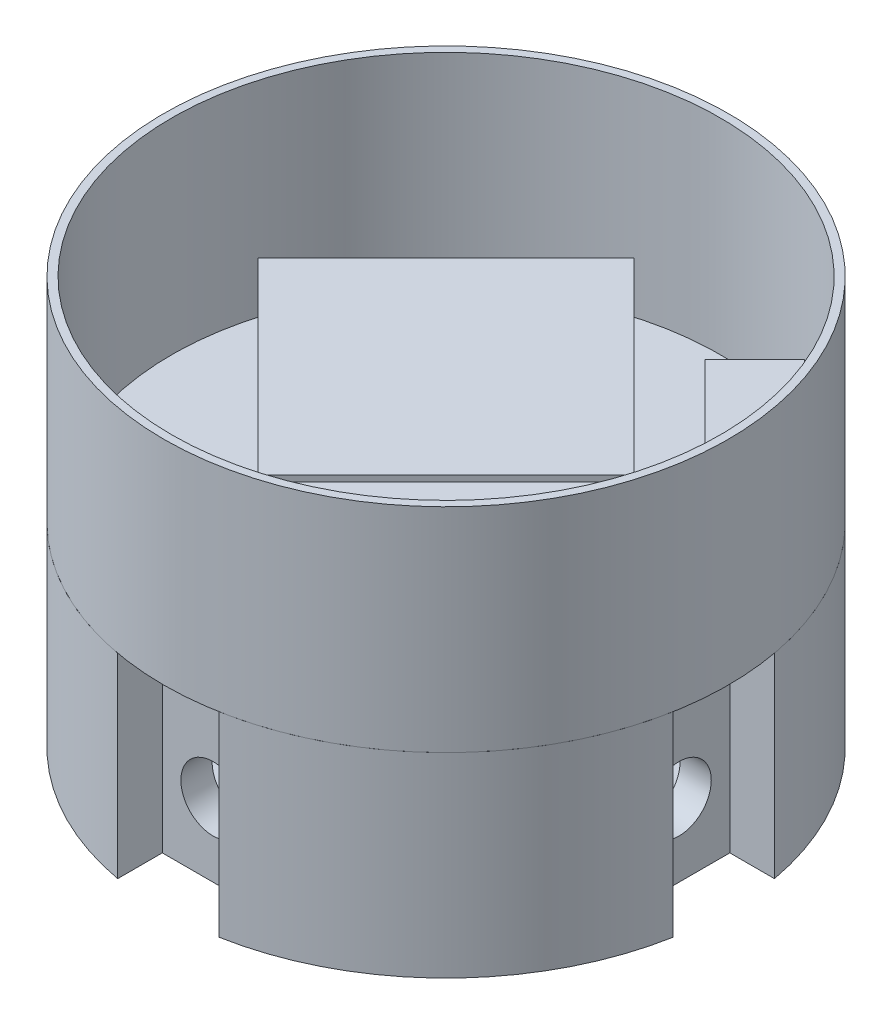
SolidWorks part; units mm, degrees
ref_plane "前基準面" through (0, 0, 0) normal (0, 0, 1) x (1, 0, 0)
ref_plane "上基準面" through (0, 0, 0) normal (0, 1, 0) x (1, 0, 0)
ref_plane "右基準面" through (0, 0, 0) normal (1, 0, 0) x (0, 0, -1)
sketch "草圖1" plane through (0, 0, 0) normal (0, 1, 0) x (1, 0, 0)
  line L0 (0, 78.355) -> (0, -92.3476) construction
  line L1 (-97.6496, 0) -> (95.3358, 0) construction
  line L21 (0, 48.0833) -> (-48.0833, 0)
  line L22 (-48.0833, 0) -> (0, -48.0833)
  line L23 (0, -48.0833) -> (48.0833, 0)
  line L24 (48.0833, 0) -> (0, 48.0833)
  line L26 (0, 0) -> (24.0416, 24.0416) construction
  circle A0 centre (0, 0) radius 72.25
  circle A1 centre (0, 0) radius 71
  circle A2 centre (0, 0) radius 68
  circle A4 centre (0, 0) radius 73 construction
  point P7 (0, 0)
  point P17 (0, 42.4264)
  point P19 (0, 0)
  point P23 (-73, 0)
  point P24 (-72.25, 0)
  point P25 (-71, 0)
  point P26 (34, 0)
  point P27 (-34, 0)
  point P28 (-68, 0)
  point P31 (42.4264, 0)
  point P32 (0, -42.4264)
  point P33 (-42.4264, 0)
  point P34 (0, 0)
  dimension "D1" = 144.5
  dimension "D5" = 142
  dimension "D6" = 3
  dimension "D8" = 146
  dimension "D2" = 68
  dimension "D3" = 4
  dimension "D4" = 4
sketch "草圖4" plane through (0, 0, 0) normal (0, 0, 1) x (1, 0, 0)
  line L0 (-34, 0) -> (-34, 102.5)
  line L1 (73, 0) -> (-73, 0) construction
  line L3 (34, 0) -> (34, 102.5)
  line L4 (34, 102.5) -> (-34, 102.5)
  line L5 (-34, 0) -> (34, 0)
  line L6 (-34, 15) -> (34, 15)
  line L7 (-34, 16.5) -> (34, 16.5)
  line L8 (-34, 31.5) -> (34, 31.5)
  line L9 (-34, 33) -> (34, 33)
  line L10 (-34, 48) -> (34, 48)
  line L11 (-34, 49.5) -> (34, 49.5)
  line L12 (-34, 64.5) -> (34, 64.5)
  line L13 (-34, 66) -> (34, 66)
  line L14 (-34, 82.5) -> (34, 82.5)
  line L15 (34, 82.5) -> (34, 81)
  line L16 (34, 81) -> (-34, 81)
  line L17 (-31.5, 31.5) -> (-31.5, 16.5)
  line L18 (-72.25, 0) -> (-72.25, 145.0993)
  line L19 (-68, 0) -> (-68, 146.8435)
  point P49 (-31.5, 16.5)
  point P52 (-31.5, 24)
  dimension "D1" = 1.5
  dimension "D2" = 15
  dimension "D3" = 1.5
  dimension "D4" = 1.5
  dimension "D5" = 1.5
  dimension "D6" = 15
  dimension "D7" = 15
  dimension "D8" = 15
  dimension "D9" = 15
  dimension "D10" = 1.5
  dimension "D11" = 20
  dimension "D12" = 53
  dimension "D19" = 102.5
sketch "草圖5" plane through (0, 0, 0) normal (0, 1, 0) x (1, 0, 0)
  line L10 (-97.6496, 0) -> (95.3358, 0) construction
  line L17 (-70.1427, 11) -> (-59.6427, 11)
  line L18 (-70.1427, 11) -> (-70.1427, -11)
  line L23 (-70.1427, -11) -> (-59.6427, -11)
  line L24 (-59.6427, 11) -> (-59.6427, -11)
  line L28 (-70.1427, 11) -> (-59.6427, -11) construction
  line L36 (-70.1427, -11) -> (-59.6427, 11) construction
  line L42 (-59.6427, 8.25) -> (-51.6427, 8.25)
  line L43 (-59.6427, 8.25) -> (-59.6427, -8.25)
  line L44 (-59.6427, -8.25) -> (-51.6427, -8.25)
  line L45 (-51.6427, 8.25) -> (-51.6427, -8.25)
  line L46 (-59.6427, 8.25) -> (-51.6427, -8.25) construction
  line L47 (-59.6427, -8.25) -> (-51.6427, 8.25) construction
  line L48 (-59.6427, 13) -> (-59.6427, -13)
  line L54 (-51.6427, 8.25) -> (-51.6427, -8.25)
  line L55 (-71.0708, 13) -> (-59.6427, 13)
  line L56 (0, 0) -> (-18.53, 0) construction
  line L57 (-71.0708, -13) -> (-59.6427, -13)
  line L58 (11, 70.1427) -> (11, 59.6427)
  line L59 (11, 70.1427) -> (-11, 70.1427)
  line L60 (-11, 70.1427) -> (-11, 59.6427)
  line L65 (11, 59.6427) -> (-11, 59.6427)
  line L66 (8.25, 59.6427) -> (8.25, 51.6427)
  line L67 (8.25, 59.6427) -> (-8.25, 59.6427)
  line L68 (-8.25, 59.6427) -> (-8.25, 51.6427)
  line L69 (8.25, 51.6427) -> (-8.25, 51.6427)
  line L70 (13, 59.6427) -> (-13, 59.6427)
  line L71 (8.25, 51.6427) -> (-8.25, 51.6427)
  line L72 (13, 71.0708) -> (13, 59.6427)
  line L73 (-13, 71.0708) -> (-13, 59.6427)
  line L74 (11, 70.1427) -> (-11, 59.6427) construction
  line L75 (-11, 70.1427) -> (11, 59.6427) construction
  line L76 (8.25, 59.6427) -> (-8.25, 51.6427) construction
  line L77 (-8.25, 59.6427) -> (8.25, 51.6427) construction
  line L78 (70.1427, -11) -> (59.6427, -11)
  line L79 (70.1427, -11) -> (70.1427, 11)
  line L80 (70.1427, 11) -> (59.6427, 11)
  line L81 (59.6427, -11) -> (59.6427, 11)
  line L82 (59.6427, -8.25) -> (51.6427, -8.25)
  line L83 (59.6427, -8.25) -> (59.6427, 8.25)
  line L84 (59.6427, 8.25) -> (51.6427, 8.25)
  line L85 (51.6427, -8.25) -> (51.6427, 8.25)
  line L86 (59.6427, -13) -> (59.6427, 13)
  line L87 (51.6427, -8.25) -> (51.6427, 8.25)
  line L88 (71.0708, -13) -> (59.6427, -13)
  line L89 (71.0708, 13) -> (59.6427, 13)
  line L90 (70.1427, -11) -> (59.6427, 11) construction
  line L91 (70.1427, 11) -> (59.6427, -11) construction
  line L92 (59.6427, -8.25) -> (51.6427, 8.25) construction
  line L93 (59.6427, 8.25) -> (51.6427, -8.25) construction
  line L94 (-11, -70.1427) -> (-11, -59.6427)
  line L95 (-11, -70.1427) -> (11, -70.1427)
  line L96 (11, -70.1427) -> (11, -59.6427)
  line L97 (-11, -59.6427) -> (11, -59.6427)
  line L98 (-8.25, -59.6427) -> (-8.25, -51.6427)
  line L99 (-8.25, -59.6427) -> (8.25, -59.6427)
  line L100 (8.25, -59.6427) -> (8.25, -51.6427)
  line L101 (-8.25, -51.6427) -> (8.25, -51.6427)
  line L102 (-13, -59.6427) -> (13, -59.6427)
  line L103 (-8.25, -51.6427) -> (8.25, -51.6427)
  line L104 (-13, -71.0708) -> (-13, -59.6427)
  line L105 (13, -71.0708) -> (13, -59.6427)
  line L106 (-11, -70.1427) -> (11, -59.6427) construction
  line L107 (11, -70.1427) -> (-11, -59.6427) construction
  line L108 (-8.25, -59.6427) -> (8.25, -51.6427) construction
  line L109 (8.25, -59.6427) -> (-8.25, -51.6427) construction
  circle A7 centre (0, 0) radius 71 construction
  circle A8 centre (0, 0) radius 72.25
  circle A10 centre (0, 0) radius 72.25
  circle A11 centre (0, 0) radius 72.25
  circle A12 centre (0, 0) radius 72.25
  circle A18 centre (0, 0) radius 72.25 construction
  point P0 (-64.8927, 0)
  point P1 (0, -54.6427)
  point P4 (54.6427, 0)
  point P8 (0, 54.6427)
  point P9 (-55.6427, 0)
  point P31 (0, 64.8927)
  point P36 (0, 55.6427)
  point P46 (64.8927, 0)
  point P51 (55.6427, 0)
  point P61 (0, -64.8927)
  point P66 (0, -55.6427)
  point P76 (0, 0)
  dimension "D1" = 10.5
  dimension "D2" = 22
  dimension "D3" = 8
  dimension "D4" = 16.5
  dimension "D5" = 2
  dimension "D6" = 4
sketch "草圖18" plane through (0, 0, 0) normal (0, 1, 0) x (-1, 0, 0)
  circle A0 centre (-30, 30) radius 1.5
  circle A1 centre (-30, 30) radius 3
  dimension "D1" = 3
  dimension "D2" = 6
sketch "草圖19" plane through (0, 0, 0) normal (0, 1, 0) x (1, 0, 0)
  line L1 (-53.8073, 26.6906) -> (-37.8073, 26.6906)
  line L2 (-53.8073, 26.6906) -> (-53.8073, 14.4906)
  line L3 (-53.8073, 14.4906) -> (-37.8073, 14.4906)
  line L4 (-37.8073, 26.6906) -> (-37.8073, 14.4906)
  line L5 (-53.8073, 26.6906) -> (-37.8073, 14.4906) construction
  line L6 (-53.8073, 14.4906) -> (-37.8073, 26.6906) construction
  line L7 (-54.8073, 27.6906) -> (-36.8073, 27.6906)
  line L8 (-54.8073, 27.6906) -> (-54.8073, 13.4906)
  line L9 (-54.8073, 13.4906) -> (-36.8073, 13.4906)
  line L10 (-36.8073, 27.6906) -> (-36.8073, 13.4906)
  line L11 (-54.8073, 27.6906) -> (-36.8073, 13.4906) construction
  line L12 (-54.8073, 13.4906) -> (-36.8073, 27.6906) construction
  point P0 (0, 0)
  point P5 (-45.8073, 20.5906)
  dimension "D1" = 16
  dimension "D2" = 12.2
  dimension "D3" = 1
  dimension "D4" = 1
  dimension "D5" = 1
  dimension "D6" = 1
sketch "草圖20" plane through (0, 0, 0) normal (0, 1, 0) x (1, 0, 0)
  circle A0 centre (-41.8475, 42.297) radius 8.5
  dimension "D1" = 17
extrude "填料-伸長1" add sketch "草圖5" along normal up to vertex (48 mm away) from offset 2 contours L105 A8 L88 L86 L81 L82 L85 L84 L89 L72 L70 L65 L66 L69 L68 L73 L55 L48 L24 L42 L45 L44 L57 L104 L102 L97 L98 L101 L100 | L45 L42 L24 L44 | L69 L66 L65 L68 | L101 L98 L97 L100 | L85 L82 L81 L84 region at (0, 0, 0) region at (-55.6427, 0, 0) region at (0, 0, -55.6427) region at (0, 0, 55.6427) region at (55.6427, 0, 0) up to point (-34, 48, 0) offset against normal yes
sketch "草圖21" plane through (-59.6427, 0, 0) normal (-1, 0, 0) x (0, 0, 1)
  circle A0 centre (0, 16.5) radius 11
  circle A1 centre (0, 16.5) radius 8.25
  dimension "D1" = 22
  dimension "D2" = 16.5
extrude "除料-伸長1" cut sketch "草圖21" against normal blind 10 contours A1 region at (-59.6427, 16.5, 0)
pattern_circular "環狀複製排列1" count 4 over 360 about axis through (0, 48, 0) along (0, -1, 0) of "除料-伸長1" reverse direction yes
sketch "草圖22" plane through (0, 0, 0) normal (0, 1, 0) x (1, 0, 0)
  line L6 (-73.8956, 51.6427) -> (61.8043, 51.6427)
  line L18 (8.25, 51.6427) -> (-8.25, 51.6427) construction
  line L19 (-136.4248, -51.6427) -> (85.6457, -51.6427)
  line L20 (-8.25, -51.6427) -> (8.25, -51.6427) construction
  line L21 (-51.6427, 67.7621) -> (-51.6427, -67.8778)
  line L22 (-51.6427, 8.25) -> (-51.6427, -8.25) construction
  line L23 (51.6427, 62.1167) -> (51.6427, -86.8537)
  line L24 (51.6427, -8.25) -> (51.6427, 8.25) construction
  circle A0 centre (0, 0) radius 68
  circle A1 centre (0, 0) radius 68 construction
extrude "填料-伸長2" add sketch "草圖1" along normal up to vertex (102.5 mm away) from surface contours A0 up to point (-34, 102.5, 0) starting at face at (0, 48, 0)
shell "薄殼3" thickness 2 removed face at (0, 102.5, 72.25)
extrude "除料-伸長3" cut sketch "草圖22" along normal up to vertex (48 mm away) from vertex contours L23 L6 L21 L19 region at (0, 0, 0) up to point (-34, 48, 0) starting at point (-34, 0, 0)
ref_plane "平面2" through (0, 0, 0) normal (0.7071, 0, 0.7071) x (0.7071, 0, -0.7071)
sketch "草圖32" plane through (0, 0, 0) normal (0.7071, 0, 0.7071) x (0.7071, 0, -0.7071)
  line L0 (-34, 0) -> (-34, 102.5)
  line L1 (-30, 102.5) -> (-30, 108.5)
  line L3 (34, 0) -> (34, 102.5)
  line L4 (34, 102.5) -> (-34, 102.5)
  line L5 (-34, 0) -> (34, 0)
  line L6 (-34, 15) -> (34, 15)
  line L7 (-34, 16.5) -> (34, 16.5)
  line L8 (-34, 31.5) -> (34, 31.5)
  line L9 (-34, 33) -> (34, 33)
  line L10 (-34, 48) -> (34, 48)
  line L11 (-34, 49.5) -> (34, 49.5)
  line L12 (-34, 64.5) -> (34, 64.5)
  line L13 (-34, 66) -> (34, 66)
  line L14 (-34, 82.5) -> (34, 82.5)
  line L15 (34, 82.5) -> (34, 81)
  line L16 (34, 81) -> (-34, 81)
  line L17 (-31.5, 31.5) -> (-31.5, 16.5)
  line L18 (-72.25, 0) -> (-72.25, 145.0993)
  line L19 (-68, 0) -> (-68, 146.8435)
  line L20 (-30, 108.5) -> (-27, 108.5)
  line L21 (-27, 108.5) -> (-27, 102.5)
  line L22 (0, 0) -> (0, 28.7574) construction
  line L23 (27, 108.5) -> (27, 102.5)
  line L24 (30, 108.5) -> (27, 108.5)
  line L25 (30, 102.5) -> (30, 108.5)
  point P49 (-31.5, 16.5)
  point P52 (-31.5, 24)
  dimension "D1" = 1.5
  dimension "D2" = 15
  dimension "D3" = 1.5
  dimension "D4" = 1.5
  dimension "D5" = 1.5
  dimension "D6" = 15
  dimension "D7" = 15
  dimension "D8" = 15
  dimension "D9" = 15
  dimension "D10" = 1.5
  dimension "D11" = 20
  dimension "D12" = 53
  dimension "D13" = 3
  dimension "D14" = 6
  dimension "D15" = 4
  dimension "D19" = 102.5
sketch "草圖33" plane through (0, 0, 0) normal (0, 1, 0) x (1, 0, 0)
  line L0 (14.039, 52.2228) -> (52.2228, 14.039)
  line L1 (14.039, 52.2228) -> (26.7669, 64.9507)
  line L2 (52.2228, 14.039) -> (64.9507, 26.7669)
  line L3 (26.7669, 64.9507) -> (64.9507, 26.7669)
  line L4 (14.039, 52.2228) -> (64.9507, 26.7669) construction
  line L5 (52.2228, 14.039) -> (26.7669, 64.9507) construction
  line L6 (48.0833, 0) -> (0, 48.0833) construction
  line L7 (-77.275, -77.275) -> (77.275, 77.275) construction
  arc A0 (68.6299, 15) -> (15, 68.6299) centre (0, 0) ccw construction
  point P1 (39.4949, 39.4949)
  dimension "D1" = 54
  dimension "D2" = 18
extrude "填料-伸長4" add sketch "草圖33" along normal blind 65 separate body
sketch "草圖35" plane through (0, 0, 0) normal (0, 1, 0) x (1, 0, 0)
  line L0 (0, 0) -> (-9.0639, 9.0639) construction
  line L1 (-27.133, 62.4884) -> (-28.1937, 63.549)
  line L2 (-27.133, 62.4884) -> (-62.4884, 27.133)
  line L3 (-62.4884, 27.133) -> (-63.549, 28.1937)
  line L4 (-28.1937, 63.549) -> (-63.549, 28.1937)
  line L5 (-27.133, 62.4884) -> (-63.549, 28.1937) construction
  line L6 (-62.4884, 27.133) -> (-28.1937, 63.549) construction
  line L7 (0, 0) -> (24.0416, 24.0416) construction
  line L9 (0, 48.0833) -> (-48.0833, 0) construction
  point P0 (-45.341, 45.341)
  point P7 (-9.6823, 9.0626)
  point P8 (-11.1956, 6.2422)
  point P11 (0, 0)
  point P12 (-44.8107, 44.8107)
  point P13 (0, 0)
  dimension "D1" = 50
  dimension "D2" = 1.5
extrude "填料-伸長6" add sketch "草圖32" along normal mid plane 68 separate body contours L16 L3 L14 L0 | L13 L0 L12 L3 | L11 L0 L10 L3 | L9 L0 L8 L3 | L6 L22 L7 L0 | L22 L6 L3 L7 region at (-12.0208, 15.75, 12.0208) region at (12.0208, 15.75, -12.0208) region at (0, 32.25, 0) region at (0, 48.75, 0) region at (0, 65.25, 0) region at (0, 81.75, 0)
sketch "草圖36" plane through (0, 0, 0) normal (0, 1, 0) x (1, 0, 0)
  line L0 (0, 78.355) -> (0, -92.3476) construction
  line L1 (-60, -20.3403) -> (60, -20.3403)
  line L2 (-60, -20.3403) -> (-60, -27.7429)
  line L3 (-60, -27.7429) -> (60, -27.7429)
  line L4 (60, -20.3403) -> (60, -27.7429)
  line L5 (-60, -20.3403) -> (60, -27.7429) construction
  line L6 (-60, -27.7429) -> (60, -20.3403) construction
  point P0 (0, -24.0416)
  point P5 (-46.7368, -20.0066)
  point P6 (98.4466, -38.9268)
  point P7 (0, -24.0416)
  dimension "D1" = 120
